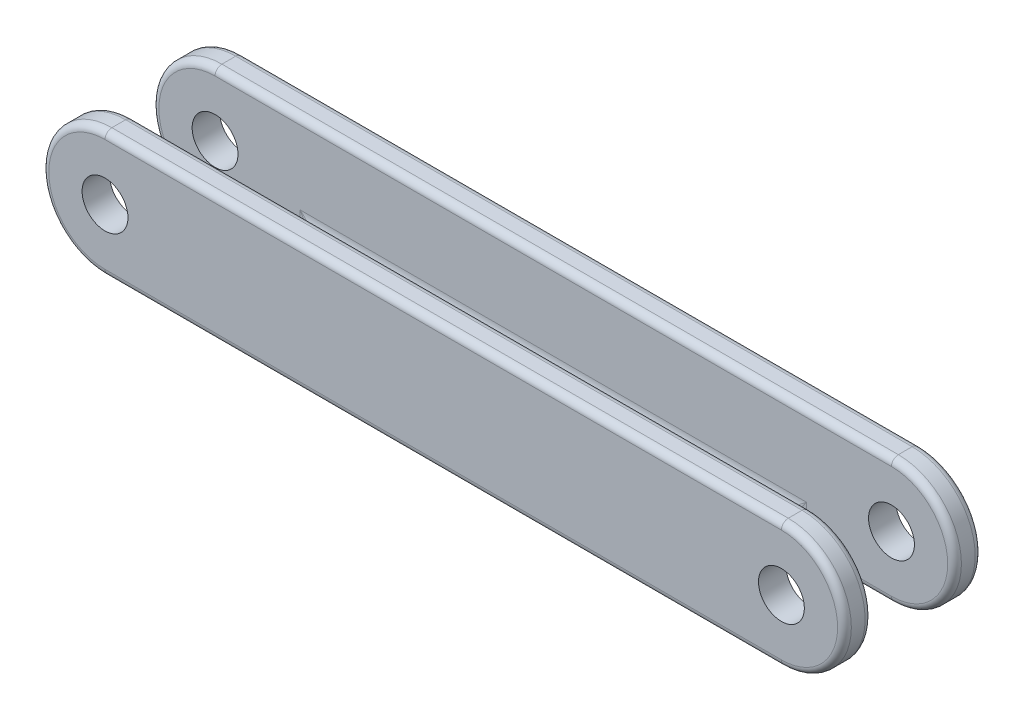
SolidWorks part; units mm, degrees
material "AISI 1020"
ref_plane "Front Plane" through (0, 0, 0) normal (0, 0, 1) x (1, 0, 0)
ref_plane "Top Plane" through (0, 0, 0) normal (0, 1, 0) x (1, 0, 0)
ref_plane "Right Plane" through (0, 0, 0) normal (1, 0, 0) x (0, 0, -1)
sketch "Sketch1" plane through (0, 0, 0) normal (1, 0, 0) x (0, 0, -1)
  line L0 (-30, 27.5) -> (-18, 27.5)
  line L1 (30, -27.5) -> (-30, -27.5)
  line L2 (30, -27.5) -> (30, 27.5)
  line L3 (30, 27.5) -> (-30, 27.5) construction
  line L4 (-30, -27.5) -> (-30, 27.5)
  line L5 (30, -27.5) -> (-30, 27.5) construction
  line L6 (30, 27.5) -> (-30, -27.5) construction
  line L7 (-18, 27.5) -> (-18, -15.5)
  line L8 (-18, -15.5) -> (18, -15.5)
  line L9 (18, -15.5) -> (18, 27.5)
  line L10 (18, 27.5) -> (30, 27.5)
  point P0 (0, 0)
  dimension "D1" = 12
  dimension "D2" = 12
  dimension "D3" = 60
  dimension "D4" = 55
extrude "Boss-Extrude1" add sketch "Sketch1" along normal blind 350
sketch "Sketch2" plane through (0, 0, 0) normal (0, 0, 1) x (1, 0, 0)
  line L0 (350, 27.5) -> (350, -27.5) construction
  line L1 (350, -27.5) -> (0, -27.5) construction
  line L2 (350, 27.5) -> (0, 27.5) construction
  line L3 (0, 27.5) -> (0, -27.5) construction
  line L4 (27.5, 27.5) -> (0, 27.5)
  line L5 (0, 27.5) -> (0, -27.5)
  line L6 (0, -27.5) -> (27.5, -27.5)
  line L7 (322.5, 27.5) -> (350, 27.5)
  line L8 (350, 27.5) -> (350, -27.5)
  line L9 (350, -27.5) -> (322.5, -27.5)
  circle A0 centre (27.5, 0) radius 10
  circle A1 centre (27.5, 0) radius 27.5
  circle A2 centre (322.5, 0) radius 27.5
  circle A3 centre (322.5, 0) radius 10
  dimension "D1" = 20
extrude "Cut-Extrude1" cut sketch "Sketch2" against normal through all both and the other way through all contours A1 L4 L5 | A1 L5 L6 | A0 | A3 | A2 L8 L7 | A2 L9 L8 region at (6.1426, 21.3574, 0) region at (6.1426, -21.3574, 0) region at (343.8574, 21.3574, 0) region at (343.8574, -21.3574, 0) region at (27.5, 0, 0) region at (322.5, 0, 0)
sketch "Sketch3" plane through (0, 0, 30) normal (0, 0, 1) x (1, 0, 0)
  line L0 (4.7844, -15.5) -> (345.2156, -15.5)
  line L1 (322.5, -27.5) -> (27.5, -27.5) construction
  line L2 (322.5, -27.5) -> (27.5, -27.5)
  line L3 (345.2156, -15.5) -> (4.7844, -15.5) construction
  line L4 (72.5, -15.5) -> (72.5, -27.5)
  line L5 (277.5, -15.5) -> (277.5, -27.5)
  arc A0 (27.5, 27.5) -> (27.5, -27.5) centre (27.5, 0) ccw construction
  arc A1 (322.5, -27.5) -> (322.5, 27.5) centre (322.5, 0) ccw construction
  arc A2 (4.7844, -15.5) -> (27.5, -27.5) centre (27.5, 0) ccw
  arc A3 (322.5, -27.5) -> (345.2156, -15.5) centre (322.5, 0) ccw
  arc M4 (27.5, 27.5) -> (27.5, -27.5) centre (27.5, 0) ccw
  line M5 (27.5, -27.5) -> (322.5, -27.5)
  arc M6 (322.5, -27.5) -> (322.5, 27.5) centre (322.5, 0) ccw
  dimension "D1" = 45
  dimension "D2" = 45
extrude "Cut-Extrude2" cut sketch "Sketch3" against normal up to surface (48 mm away) from surface contours L4 L0 M4 M5 | L0 L5 M5 M6 region at (41.7967, -21.2128, 30) region at (308.2033, -21.2128, 30) up to face at (17.5, 0, -18) starting at face at (27.5, -10, 18)
fillet "Fillet2" radius 8 6 edges at (175, -15.5, 18) (175, -15.5, -18) (277.5, -21.5, 18) (277.5, -21.5, -18) (72.5, -21.5, 18) (72.5, -21.5, -18)
fillet "Fillet1" radius 3 30 edges at (350, 0, -30) (175, -27.5, -30) (0, 0, -30) (350, 0, -18) (0, 0, -18) (0, 0, 18) (175, 27.5, 18) (175, -27.5, 30) (0, 0, 30) (175, 27.5, 30) (175, 27.5, -30) (175, 27.5, -18) (350, 0, 18) (350, 0, 30) (304, -27.5, -18) (46, -27.5, -18) (304, -27.5, 18) (46, -27.5, 18) (279.8431, -27.5, 15.6569) (277.5, -27.5, 0) (279.8431, -27.5, -15.6569) (70.1569, -27.5, -15.6569) (72.5, -27.5, 0) (70.1569, -27.5, 15.6569) (279.8431, -13.1569, -15.6569) (279.8431, -13.1569, 15.6569) (70.1569, -13.1569, -15.6569) (70.1569, -13.1569, 15.6569) (277.5, -15.5, 0) (72.5, -15.5, 0)
